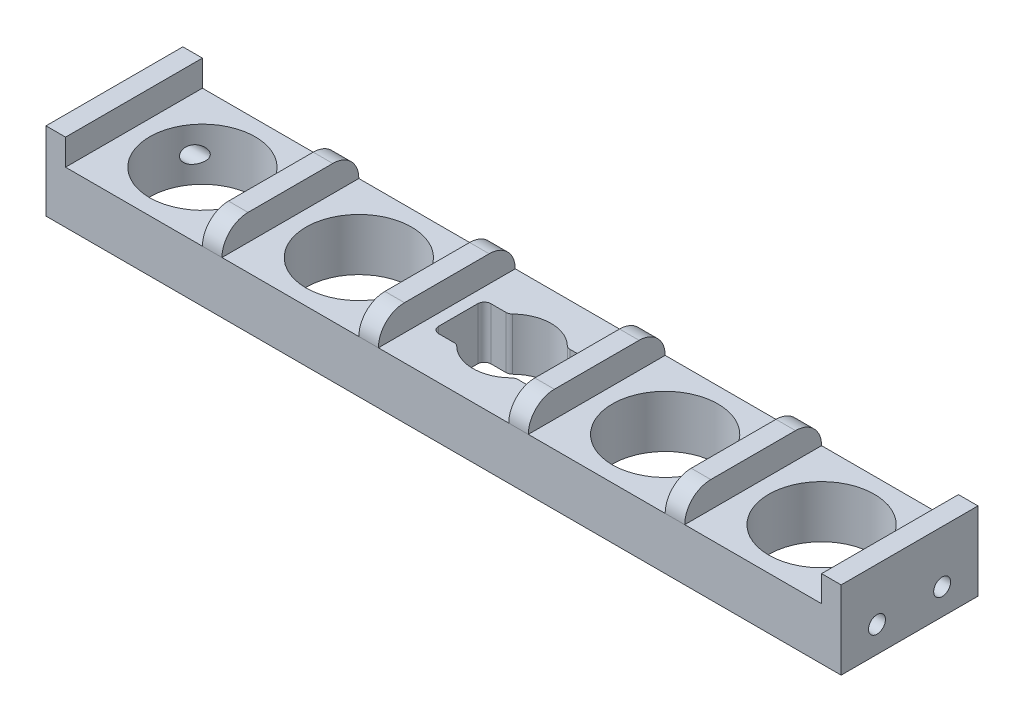
SolidWorks part; units mm, degrees
ref_plane "Front Plane" through (0, 0, 0) normal (0, 0, 1) x (1, 0, 0)
ref_plane "Top Plane" through (0, 0, 0) normal (0, 1, 0) x (1, 0, 0)
ref_plane "Right Plane" through (0, 0, 0) normal (1, 0, 0) x (0, 0, -1)
sketch "Sketch1" plane through (0, 0, 0) normal (0, 1, 0) x (1, 0, 0)
  line L1 (-61, 10.5) -> (61, 10.5)
  line L2 (-61, 10.5) -> (-61, -10.5)
  line L3 (-61, -10.5) -> (61, -10.5)
  line L4 (61, 10.5) -> (61, -10.5)
  line L5 (-61, 10.5) -> (61, -10.5) construction
  line L6 (-61, -10.5) -> (61, 10.5) construction
  circle A0 centre (23.5, 0) radius 10 construction
  circle A1 centre (47.5, 0) radius 10 construction
  circle A2 centre (-23.5, 0) radius 10 construction
  circle A3 centre (-47.5, 0) radius 10 construction
  circle A4 centre (-47.5, 0) radius 8.1
  circle A5 centre (-23.5, 0) radius 8.1
  circle A6 centre (23.5, 0) radius 8.1
  circle A7 centre (47.5, 0) radius 8.1
  point P0 (0, 0)
  dimension "D3" = 20
  dimension "D8" = 16.2
  dimension "D1" = 122
  dimension "D2" = 21
  dimension "D4" = 24
  dimension "D5" = 13.5
  dimension "D6" = 13.5
  dimension "D7" = 24
extrude "Boss-Extrude1" add sketch "Sketch1" along normal blind 8
sketch "Sketch4" plane through (0, 8, 0) normal (0, 1, 0) x (1, 0, 0)
  line L6 (-8.25, 4) -> (8.25, 4)
  line L7 (-8.25, 4) -> (-8.25, -4)
  line L8 (-8.25, -4) -> (8.25, -4)
  line L9 (8.25, 4) -> (8.25, -4)
  line L10 (-8.25, 4) -> (8.25, -4) construction
  line L11 (-8.25, -4) -> (8.25, 4) construction
  circle A0 centre (0, 0) radius 6
  point P0 (0, 0)
  dimension "D3" = 12
  dimension "D1" = 8
  dimension "D2" = 16.5
extrude "Cut-Extrude1" cut sketch "Sketch4" against normal blind 122 contours A0 L8 L9 L6 | L8 A0 L6 | L6 A0 | L8 A0 | A0 L6 L7 L8 region at (-6.8487, 8, 0) region at (0, 8, -4.8127) region at (0, 8, 0) region at (6.8487, 8, 0) region at (0, 8, 4.8127)
fillet "Fillet2" radius 1 8 edges at (-8.25, 4, 4) (-4.4721, 4, 4) (4.4721, 4, 4) (8.25, 4, 4) (8.25, 4, -4) (4.4721, 4, -4) (-4.4721, 4, -4) (-8.25, 4, -4)
sketch "Sketch6" plane through (0, 8, 0) normal (0, 1, 0) x (1, 0, 0)
  line L0 (-61, -10.5) -> (61, -10.5) construction
  line L1 (-61, 10.5) -> (-58, 10.5)
  line L2 (-61, 10.5) -> (-61, -10.5)
  line L3 (-61, -10.5) -> (-58, -10.5)
  line L4 (-58, 10.5) -> (-58, -10.5)
  line L5 (61, 10.5) -> (-61, 10.5) construction
  line L6 (-37, 10.5) -> (-34, 10.5)
  line L7 (-37, 10.5) -> (-37, -10.5)
  line L8 (-37, -10.5) -> (-34, -10.5)
  line L9 (-34, 10.5) -> (-34, -10.5)
  line L10 (-35.5, 10.5) -> (-35.5, -10.5) construction
  line L19 (34, 10.5) -> (37, 10.5)
  line L20 (34, 10.5) -> (34, -10.5)
  line L21 (34, -10.5) -> (37, -10.5)
  line L22 (37, 10.5) -> (37, -10.5)
  line L23 (61, 10.5) -> (58, 10.5)
  line L24 (61, 10.5) -> (61, -10.5)
  line L25 (61, -10.5) -> (58, -10.5)
  line L26 (58, 10.5) -> (58, -10.5)
  line L27 (-59.5, 10.5) -> (-59.5, -10.5) construction
  line L28 (-11.5, 10.5) -> (-11.5, -10.5) construction
  line L29 (35.5, -10.5) -> (35.5, 10.5) construction
  line L30 (-13, 10.5) -> (-10, 10.5)
  line L31 (-13, 10.5) -> (-13, -10.5)
  line L32 (-13, -10.5) -> (-10, -10.5)
  line L33 (-10, 10.5) -> (-10, -10.5)
  line L34 (10, 10.5) -> (13, 10.5)
  line L35 (10, 10.5) -> (10, -10.5)
  line L36 (10, -10.5) -> (13, -10.5)
  line L37 (13, 10.5) -> (13, -10.5)
  line L38 (11.5, -10.5) -> (11.5, 10.5) construction
  circle A0 centre (-47.5, 0) radius 8.1 construction
  circle A2 centre (47.5, 0) radius 8.1 construction
  circle A3 centre (-23.5, 0) radius 8.1 construction
  circle A4 centre (23.5, 0) radius 8.1 construction
  dimension "D4" = 12
  dimension "D1" = 3
  dimension "D2" = 3
  dimension "D3" = 12
  dimension "D5" = 3
  dimension "D6" = 3
  dimension "D7" = 12
  dimension "D8" = 12
  dimension "D9" = 3
  dimension "D10" = 3
extrude "Boss-Extrude4" add sketch "Sketch6" along normal blind 4
fillet "Fillet3" radius 4 8 edges at (35.5, 12, 10.5) (11.5, 12, 10.5) (-11.5, 12, 10.5) (-35.5, 12, 10.5) (35.5, 12, -10.5) (11.5, 12, -10.5) (-11.5, 12, -10.5) (-35.5, 12, -10.5)
sketch "Sketch7" plane through (61, 0, 0) normal (1, 0, 0) x (0, 0, -1)
  line L0 (-10.5, 0) -> (10.5, 0) construction
  circle A0 centre (-5, 4) radius 1.3
  circle A1 centre (5, 4) radius 1.3
  dimension "D4" = 2.6
  dimension "D1" = 4
  dimension "D2" = 5
  dimension "D3" = 5
extrude "Cut-Extrude2" cut sketch "Sketch7" against normal blind 10
mirror "Mirror1" about plane through (0, 0, 0) normal (1, 0, 0) of "Cut-Extrude2"
